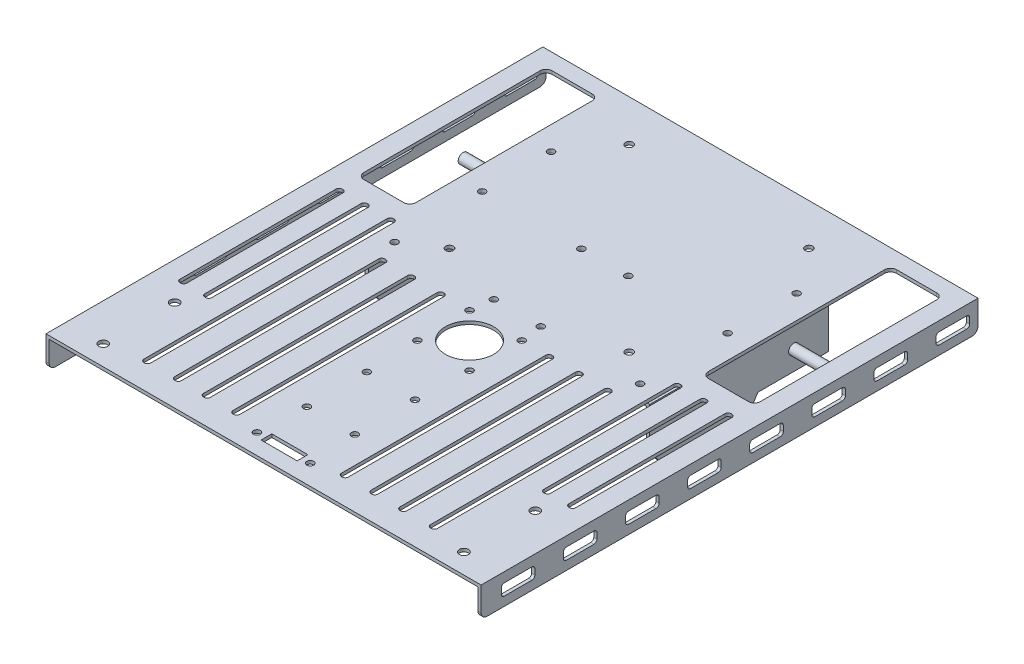
SolidWorks part; units mm, degrees
ref_plane "Front Plane" through (0, 0, 0) normal (0, 0, 1) x (1, 0, 0)
ref_plane "Top Plane" through (0, 0, 0) normal (0, 1, 0) x (1, 0, 0)
ref_plane "Right Plane" through (0, 0, 0) normal (1, 0, 0) x (0, 0, -1)
sketch "Sketch2" plane through (0, 0, 0) normal (0, 1, 0) x (1, 0, 0)
  line L7 (-172.2662, -88.2141) -> (41.7338, -88.2141)
  line L48 (-164.2662, 151.7859) -> (-138.2662, 151.7859)
  line L49 (-164.2662, 151.7859) -> (-164.2662, 57.7859)
  line L50 (-164.2662, 57.7859) -> (-138.2662, 57.7859)
  line L51 (-138.2662, 151.7859) -> (-138.2662, 57.7859)
  line L72 (41.7338, 159.7859) -> (-172.2662, 159.7859)
  line L75 (-65.2662, 159.7859) -> (-65.2662, -88.2141) construction
  line L76 (41.7338, -88.2141) -> (41.7338, 159.7859)
  line L77 (7.7338, 151.7859) -> (7.7338, 57.7859)
  line L78 (33.7338, 57.7859) -> (7.7338, 57.7859)
  line L79 (-172.2662, -88.2141) -> (-172.2662, 159.7859)
  line L80 (33.7338, 151.7859) -> (33.7338, 57.7859)
  line L81 (33.7338, 151.7859) -> (7.7338, 151.7859)
  point P2 (-151.2662, 151.7859)
  dimension "D1" = 8
  dimension "D3" = 8
  dimension "D6" = 107
  dimension "D9" = 26
extrude "Boss-Extrude1" add sketch "Sketch2" along normal blind 1.6
ref_plane "Plane3" through (-65.2662, 0, 0) normal (-1, 0, 0) x (0, 0, 1)
sketch "Sketch4" plane through (0, 0, 0) normal (0, -1, 0) x (1, 0, 0)
  line L5 (-172.2662, 15.9553) -> (41.7338, 15.9553) construction
  line L6 (-172.2662, -159.7859) -> (-172.2662, 88.2141) construction
  line L7 (41.7338, 88.2141) -> (41.7338, -159.7859) construction
  point P6 (-65.2662, 15.9553)
  line B0 (-136.2673, -122.8126) -> (-136.2673, -33.5103)
  line B1 (-136.2673, -122.8126) -> (-118.4267, -122.8126)
  line B2 (-136.2673, -33.5103) -> (-118.4299, -33.5103)
  line B3 (-72.7662, -32.9867) -> (-72.7662, -87.1773)
  line B4 (-72.7662, -32.9867) -> (-81.1807, -32.9867)
  line B5 (-72.7662, -87.1773) -> (-81.1807, -87.1773)
  line B6 (-118.4299, -33.5103) -> (-118.4299, -55.4044)
  line B7 (-118.4299, -55.4044) -> (-81.1807, -55.4044)
  line B8 (-81.1807, -55.4044) -> (-81.1807, -32.9867)
  line B9 (-81.1807, -87.1773) -> (-81.1807, -65.4044)
  line B10 (-81.1807, -65.4044) -> (-118.4267, -65.4044)
  line B11 (-118.4267, -65.4044) -> (-118.4267, -122.8126)
  dimension "D1" = 7.5
sketch_block_instance "Block1-1"
sketch_block "Block1"
extrude "Boss-Extrude3" add sketch "Sketch4" along normal blind 1.6129 separate body
sketch "Sketch6" plane through (-136.2673, 113.8349, 0) normal (1, 0, 0) x (0, -1, 0)
  line L0 (115.4478, 33.5103) -> (113.8349, 33.5103)
  line L1 (113.8349, 33.5103) -> (113.8349, 122.8126)
  line L4 (132.89, 33.5103) -> (115.4478, 33.5103)
  line L7 (135.5889, 122.8126) -> (113.8349, 122.8126)
  line L8 (113.8349, 57.7859) -> (113.8349, 151.7859) construction
  line L10 (115.4478, 122.8126) -> (113.8349, 122.8126) construction
  line L11 (135.5889, 122.8126) -> (135.5889, 87.5048)
  circle A2 centre (133.4041, 73.86) radius 1.27
  circle A4 centre (133.4041, 51.6858) radius 3
  circle A5 centre (125.8349, 105.4126) radius 2.55
  circle A6 centre (123.1933, 51.6858) radius 1.27
  circle A8 centre (143.6149, 51.6858) radius 1.27
  arc A10 (135.5889, 87.5048) -> (132.89, 33.5103) centre (121.2431, 61.1572) cw
  line M25 (113.8349, 33.5103) -> (113.8349, 122.8126)
  line M26 (113.8349, 122.8126) -> (115.4478, 122.8126)
  line M27 (115.4478, 122.8126) -> (115.4478, 33.5103)
  line M28 (115.4478, 33.5103) -> (113.8349, 33.5103)
  dimension "D1" = 5.1
  dimension "D3" = 17.4
  dimension "D4" = 6
  dimension "D2" = 12
extrude "Boss-Extrude4" add sketch "Sketch6" along normal blind 1.6129 contours M28 M25 M26 M27 | L4 M27 | A6 A2 A4 A8 region at (-136.2673, -15.7003, -74.0989) region at (-136.2673, -0.8065, -78.1615)
sketch "Sketch7" plane through (0, 0, 0) normal (0, -1, 0) x (1, 0, 0)
  line L0 (-172.2662, 88.2141) -> (41.7338, 88.2141) construction
  line L1 (-65.2662, -2.5939) -> (-65.2662, -26.5939)
  line L48 (-65.2662, -1159.7859) -> (-65.2662, 48840.2141) construction
  line L49 (41.7338, -159.7859) -> (-172.2662, -159.7859) construction
  line L50 (-65.2662, 80.4578) -> (-65.2662, 75.1009)
  line L51 (-65.2662, 80.4578) -> (-74.2715, 80.4578)
  line L52 (-65.2662, 75.1009) -> (-74.2715, 75.1009)
  line L53 (-74.2715, 80.4578) -> (-74.2715, 75.1009)
  circle A0 centre (-126.541, -82.125) radius 1.7
  circle A1 centre (-126.541, -38.4299) radius 1.7
  circle A2 centre (-76.9723, -38.4299) radius 1.7
  circle A3 centre (-76.9723, -82.125) radius 1.7
  circle A4 centre (-126.541, -116.5476) radius 1.7
  circle A5 centre (-110.1162, -49.4299) radius 1.9
  circle A6 centre (-110.1162, -139.1299) radius 1.9
  circle A7 centre (-155.2662, 42.5701) radius 2.25
  circle A8 centre (-78.2662, -1.5939) radius 1.7
  circle A9 centre (-78.2662, -27.5939) radius 1.7
  arc A11 (-65.2662, -2.5939) -> (-65.2662, -26.5939) centre (-65.2662, -14.5939) ccw
  circle A12 centre (-78.5662, 78.2141) radius 1.7
  circle A13 centre (-77.2662, 24.6349) radius 1.7
  circle A14 centre (-77.2662, 54.6349) radius 1.7
  circle A15 centre (-155.2662, 78.2141) radius 2.25
  point P38 (-65.2662, -159.7859)
  dimension "D3" = 3.4
  dimension "D4" = 3.4
  dimension "D5" = 3.4
  dimension "D6" = 3.4
  dimension "D1" = 3.4
  dimension "D2" = 3.8
  dimension "D8" = 3.8
  dimension "D9" = 4.5
  dimension "D12" = 3.4
  dimension "D13" = 3.4
  dimension "D14" = 12
  dimension "D20" = 3.4
  dimension "D23" = 3.4
  dimension "D24" = 3.4
  dimension "D22" = 10
  dimension "D25" = 30
  dimension "D15" = 13
  dimension "D19" = 12
  dimension "D21" = 13.3
  dimension "D11" = 89.7
  dimension "D17" = 13
  dimension "D18" = 26
  dimension "D7" = 92
  dimension "D16" = 44.85
  dimension "D26" = 11.7061
  dimension "D27" = 49.5687
  dimension "D10" = 90
  dimension "D28" = 34.836
extrude "Cut-Extrude1" cut sketch "Sketch7" against normal blind 10 and the other way blind 10
mirror "Mirror1" about plane through (-65.2662, 0, 0) normal (-1, 0, 0) of bodies 157 158 103
mirror "Mirror2" about plane through (-65.2662, 0, 0) normal (-1, 0, 0) of "Cut-Extrude1"
sketch "Sketch9" plane through (-138.2662, 0, 0) normal (1, 0, 0) x (0, 0, -1)
  circle A0 centre (105.4126, -12) radius 2.5
extrude "Boss-Extrude6" add sketch "Sketch9" along normal blind 169 and the other way blind 21 separate body
sketch "Sketch11" plane through (0, 1.6, 0) normal (0, 1, 0) x (1, 0, 0)
  line L0 (-172.2662, 159.7859) -> (-172.2662, -88.2141)
  line L1 (-172.2662, 159.7859) -> (-173.8662, 159.7859)
  line L2 (-172.2662, -88.2141) -> (-173.8662, -88.2141)
  line L3 (-173.8662, 159.7859) -> (-173.8662, -88.2141)
  line L4 (41.7338, 159.7859) -> (41.7338, -88.2141)
  line L5 (41.7338, 159.7859) -> (43.3338, 159.7859)
  line L6 (41.7338, -88.2141) -> (43.3338, -88.2141)
  line L7 (43.3338, 159.7859) -> (43.3338, -88.2141)
  dimension "D1" = 1.6
  dimension "D2" = 1.6
extrude "Boss-Extrude7" add sketch "Sketch11" against normal blind 15
sketch "Sketch12" plane through (0, 1.6, 0) normal (0, 1, 0) x (1, 0, 0)
  line L12 (-65.2662, -1088.2141) -> (-65.2662, 48911.7859) construction
  line L13 (-173.8662, -88.2141) -> (43.3338, -88.2141) construction
  line L30 (-164.0365, 46.7422) -> (-164.0365, -31.2149)
  line L31 (-162.5365, 48.2422) -> (-162.1365, 48.2422)
  line L32 (-162.5365, -32.7149) -> (-162.1365, -32.7149)
  line L33 (-160.6365, 46.7422) -> (-160.6365, -31.2149)
  line L34 (-151.5274, 46.7422) -> (-151.5274, -31.2149)
  line L35 (-150.0274, 48.2422) -> (-149.6274, 48.2422)
  line L36 (-150.0274, -32.7149) -> (-149.6274, -32.7149)
  line L37 (-148.1274, 46.7422) -> (-148.1274, -31.2149)
  line L38 (-138.5117, 46.7422) -> (-138.5117, -74.7128)
  line L39 (-137.0117, 48.2422) -> (-136.6117, 48.2422)
  line L40 (-137.0117, -76.2128) -> (-136.6117, -76.2128)
  line L41 (-135.1117, 46.7422) -> (-135.1117, -74.7128)
  line L42 (-123.2237, 27.2471) -> (-123.2237, -74.7128)
  line L43 (-121.7237, 28.7471) -> (-121.3237, 28.7471)
  line L44 (-121.7237, -76.2128) -> (-121.3237, -76.2128)
  line L45 (-119.8237, 27.2471) -> (-119.8237, -74.7128)
  line L46 (-108.7986, 27.2471) -> (-108.7986, -74.7128)
  line L47 (-107.2986, 28.7471) -> (-106.8986, 28.7471)
  line L48 (-107.2986, -76.2128) -> (-106.8986, -76.2128)
  line L49 (-105.3986, 27.2471) -> (-105.3986, -74.7128)
  line L50 (-94.0418, 27.2471) -> (-94.0418, -74.7128)
  line L51 (-92.5418, 28.7471) -> (-92.1418, 28.7471)
  line L52 (-92.5418, -76.2128) -> (-92.1418, -76.2128)
  line L53 (-90.6418, 27.2471) -> (-90.6418, -74.7128)
  line L54 (-39.8906, 27.2471) -> (-39.8906, -74.7128)
  line L55 (-37.9906, -76.2128) -> (-38.3906, -76.2128)
  line L56 (-37.9906, 28.7471) -> (-38.3906, 28.7471)
  line L57 (-36.4906, 27.2471) -> (-36.4906, -74.7128)
  line L58 (-25.1338, 27.2471) -> (-25.1338, -74.7128)
  line L59 (-23.2338, -76.2128) -> (-23.6338, -76.2128)
  line L60 (-23.2338, 28.7471) -> (-23.6338, 28.7471)
  line L61 (-21.7338, 27.2471) -> (-21.7338, -74.7128)
  line L62 (-10.7087, 27.2471) -> (-10.7087, -74.7128)
  line L63 (-8.8087, -76.2128) -> (-9.2087, -76.2128)
  line L64 (-8.8087, 28.7471) -> (-9.2087, 28.7471)
  line L65 (-7.3087, 27.2471) -> (-7.3087, -74.7128)
  line L66 (4.5793, 46.7422) -> (4.5793, -74.7128)
  line L67 (6.4793, -76.2128) -> (6.0793, -76.2128)
  line L68 (6.4793, 48.2422) -> (6.0793, 48.2422)
  line L69 (7.9793, 46.7422) -> (7.9793, -74.7128)
  line L70 (17.5951, 46.7422) -> (17.5951, -31.2149)
  line L71 (19.4951, -32.7149) -> (19.0951, -32.7149)
  line L72 (19.4951, 48.2422) -> (19.0951, 48.2422)
  line L73 (20.9951, 46.7422) -> (20.9951, -31.2149)
  line L74 (30.1041, 46.7422) -> (30.1041, -31.2149)
  line L75 (32.0041, -32.7149) -> (31.6041, -32.7149)
  line L76 (32.0041, 48.2422) -> (31.6041, 48.2422)
  line L77 (33.5041, 46.7422) -> (33.5041, -31.2149)
  arc A0 (-94.0418, -74.7128) -> (-92.5418, -76.2128) centre (-92.5418, -74.7128) ccw
  arc A1 (-92.1418, -76.2128) -> (-90.6418, -74.7128) centre (-92.1418, -74.7128) ccw
  arc A2 (-92.1418, 28.7471) -> (-90.6418, 27.2471) centre (-92.1418, 27.2471) cw
  arc A3 (-94.0418, 27.2471) -> (-92.5418, 28.7471) centre (-92.5418, 27.2471) cw
  arc A4 (-108.7986, 27.2471) -> (-107.2986, 28.7471) centre (-107.2986, 27.2471) cw
  arc A5 (-106.8986, 28.7471) -> (-105.3986, 27.2471) centre (-106.8986, 27.2471) cw
  arc A6 (-106.8986, -76.2128) -> (-105.3986, -74.7128) centre (-106.8986, -74.7128) ccw
  arc A7 (-108.7986, -74.7128) -> (-107.2986, -76.2128) centre (-107.2986, -74.7128) ccw
  arc A8 (-123.2237, -74.7128) -> (-121.7237, -76.2128) centre (-121.7237, -74.7128) ccw
  arc A9 (-121.3237, -76.2128) -> (-119.8237, -74.7128) centre (-121.3237, -74.7128) ccw
  arc A10 (-121.3237, 28.7471) -> (-119.8237, 27.2471) centre (-121.3237, 27.2471) cw
  arc A11 (-123.2237, 27.2471) -> (-121.7237, 28.7471) centre (-121.7237, 27.2471) cw
  arc A12 (-138.5117, -74.7128) -> (-137.0117, -76.2128) centre (-137.0117, -74.7128) ccw
  arc A13 (-136.6117, -76.2128) -> (-135.1117, -74.7128) centre (-136.6117, -74.7128) ccw
  arc A14 (-136.6117, 48.2422) -> (-135.1117, 46.7422) centre (-136.6117, 46.7422) cw
  arc A15 (-138.5117, 46.7422) -> (-137.0117, 48.2422) centre (-137.0117, 46.7422) cw
  arc A16 (-151.5274, 46.7422) -> (-150.0274, 48.2422) centre (-150.0274, 46.7422) cw
  arc A17 (-149.6274, 48.2422) -> (-148.1274, 46.7422) centre (-149.6274, 46.7422) cw
  arc A18 (-149.6274, -32.7149) -> (-148.1274, -31.2149) centre (-149.6274, -31.2149) ccw
  arc A19 (-151.5274, -31.2149) -> (-150.0274, -32.7149) centre (-150.0274, -31.2149) ccw
  arc A20 (-164.0365, -31.2149) -> (-162.5365, -32.7149) centre (-162.5365, -31.2149) ccw
  arc A21 (-162.1365, -32.7149) -> (-160.6365, -31.2149) centre (-162.1365, -31.2149) ccw
  arc A22 (-162.1365, 48.2422) -> (-160.6365, 46.7422) centre (-162.1365, 46.7422) cw
  arc A23 (-162.5365, 48.2422) -> (-164.0365, 46.7422) centre (-162.5365, 46.7422) ccw
  arc A24 (32.0041, 48.2422) -> (33.5041, 46.7422) centre (32.0041, 46.7422) cw
  arc A25 (31.6041, 48.2422) -> (30.1041, 46.7422) centre (31.6041, 46.7422) ccw
  arc A26 (31.6041, -32.7149) -> (30.1041, -31.2149) centre (31.6041, -31.2149) cw
  arc A27 (33.5041, -31.2149) -> (32.0041, -32.7149) centre (32.0041, -31.2149) cw
  arc A28 (20.9951, -31.2149) -> (19.4951, -32.7149) centre (19.4951, -31.2149) cw
  arc A29 (19.0951, -32.7149) -> (17.5951, -31.2149) centre (19.0951, -31.2149) cw
  arc A30 (19.0951, 48.2422) -> (17.5951, 46.7422) centre (19.0951, 46.7422) ccw
  arc A31 (20.9951, 46.7422) -> (19.4951, 48.2422) centre (19.4951, 46.7422) ccw
  arc A32 (7.9793, 46.7422) -> (6.4793, 48.2422) centre (6.4793, 46.7422) ccw
  arc A33 (6.0793, 48.2422) -> (4.5793, 46.7422) centre (6.0793, 46.7422) ccw
  arc A34 (6.0793, -76.2128) -> (4.5793, -74.7128) centre (6.0793, -74.7128) cw
  arc A35 (7.9793, -74.7128) -> (6.4793, -76.2128) centre (6.4793, -74.7128) cw
  arc A36 (-7.3087, 27.2471) -> (-8.8087, 28.7471) centre (-8.8087, 27.2471) ccw
  arc A37 (-9.2087, 28.7471) -> (-10.7087, 27.2471) centre (-9.2087, 27.2471) ccw
  arc A38 (-9.2087, -76.2128) -> (-10.7087, -74.7128) centre (-9.2087, -74.7128) cw
  arc A39 (-7.3087, -74.7128) -> (-8.8087, -76.2128) centre (-8.8087, -74.7128) cw
  arc A40 (-21.7338, -74.7128) -> (-23.2338, -76.2128) centre (-23.2338, -74.7128) cw
  arc A41 (-23.6338, -76.2128) -> (-25.1338, -74.7128) centre (-23.6338, -74.7128) cw
  arc A42 (-23.6338, 28.7471) -> (-25.1338, 27.2471) centre (-23.6338, 27.2471) ccw
  arc A43 (-21.7338, 27.2471) -> (-23.2338, 28.7471) centre (-23.2338, 27.2471) ccw
  arc A44 (-36.4906, 27.2471) -> (-37.9906, 28.7471) centre (-37.9906, 27.2471) ccw
  arc A45 (-38.3906, 28.7471) -> (-39.8906, 27.2471) centre (-38.3906, 27.2471) ccw
  arc A46 (-38.3906, -76.2128) -> (-39.8906, -74.7128) centre (-38.3906, -74.7128) cw
  arc A47 (-36.4906, -74.7128) -> (-37.9906, -76.2128) centre (-37.9906, -74.7128) cw
  point P41 (-65.2662, -88.2141)
  dimension "D1" = 1.5
extrude "Cut-Extrude2" cut sketch "Sketch12" against normal blind 8
sketch "Sketch13" plane through (-173.8662, 0, 0) normal (-1, 0, 0) x (0, 0, 1)
  line L0 (-154.0943, -3.2309) -> (-140.3411, -3.2309)
  line L1 (-155.5943, -4.7309) -> (-155.5943, -7.4516)
  line L2 (-138.8411, -4.7309) -> (-138.8411, -7.4516)
  line L3 (-154.0943, -8.9516) -> (-140.3411, -8.9516)
  line L4 (-107.8411, -4.7309) -> (-107.8411, -7.4516)
  line L5 (-123.0943, -8.9516) -> (-109.3411, -8.9516)
  line L6 (-124.5943, -4.7309) -> (-124.5943, -7.4516)
  line L7 (-123.0943, -3.2309) -> (-109.3411, -3.2309)
  line L8 (-76.8411, -4.7309) -> (-76.8411, -7.4516)
  line L9 (-92.0943, -8.9516) -> (-78.3411, -8.9516)
  line L10 (-93.5943, -4.7309) -> (-93.5943, -7.4516)
  line L11 (-92.0943, -3.2309) -> (-78.3411, -3.2309)
  line L12 (-45.8411, -4.7309) -> (-45.8411, -7.4516)
  line L13 (-61.0943, -8.9516) -> (-47.3411, -8.9516)
  line L14 (-62.5943, -4.7309) -> (-62.5943, -7.4516)
  line L15 (-61.0943, -3.2309) -> (-47.3411, -3.2309)
  line L16 (-14.8411, -4.7309) -> (-14.8411, -7.4516)
  line L17 (-30.0943, -8.9516) -> (-16.3411, -8.9516)
  line L18 (-31.5943, -4.7309) -> (-31.5943, -7.4516)
  line L19 (-30.0943, -3.2309) -> (-16.3411, -3.2309)
  line L20 (16.1589, -4.7309) -> (16.1589, -7.4516)
  line L21 (0.9057, -8.9516) -> (14.6589, -8.9516)
  line L22 (-0.5943, -4.7309) -> (-0.5943, -7.4516)
  line L23 (0.9057, -3.2309) -> (14.6589, -3.2309)
  line L24 (47.1589, -4.7309) -> (47.1589, -7.4516)
  line L25 (31.9057, -8.9516) -> (45.6589, -8.9516)
  line L26 (30.4057, -4.7309) -> (30.4057, -7.4516)
  line L27 (31.9057, -3.2309) -> (45.6589, -3.2309)
  line L28 (78.1589, -4.7309) -> (78.1589, -7.4516)
  line L29 (62.9057, -8.9516) -> (76.6589, -8.9516)
  line L30 (61.4057, -4.7309) -> (61.4057, -7.4516)
  line L31 (62.9057, -3.2309) -> (76.6589, -3.2309)
  arc A0 (-155.5943, -7.4516) -> (-154.0943, -8.9516) centre (-154.0943, -7.4516) ccw
  arc A1 (-138.8411, -7.4516) -> (-140.3411, -8.9516) centre (-140.3411, -7.4516) cw
  arc A2 (-140.3411, -3.2309) -> (-138.8411, -4.7309) centre (-140.3411, -4.7309) cw
  arc A3 (-155.5943, -4.7309) -> (-154.0943, -3.2309) centre (-154.0943, -4.7309) cw
  arc A4 (-107.8411, -7.4516) -> (-109.3411, -8.9516) centre (-109.3411, -7.4516) cw
  arc A5 (-124.5943, -7.4516) -> (-123.0943, -8.9516) centre (-123.0943, -7.4516) ccw
  arc A6 (-124.5943, -4.7309) -> (-123.0943, -3.2309) centre (-123.0943, -4.7309) cw
  arc A7 (-109.3411, -3.2309) -> (-107.8411, -4.7309) centre (-109.3411, -4.7309) cw
  arc A8 (-76.8411, -7.4516) -> (-78.3411, -8.9516) centre (-78.3411, -7.4516) cw
  arc A9 (-93.5943, -7.4516) -> (-92.0943, -8.9516) centre (-92.0943, -7.4516) ccw
  arc A10 (-93.5943, -4.7309) -> (-92.0943, -3.2309) centre (-92.0943, -4.7309) cw
  arc A11 (-78.3411, -3.2309) -> (-76.8411, -4.7309) centre (-78.3411, -4.7309) cw
  arc A12 (-45.8411, -7.4516) -> (-47.3411, -8.9516) centre (-47.3411, -7.4516) cw
  arc A13 (-62.5943, -7.4516) -> (-61.0943, -8.9516) centre (-61.0943, -7.4516) ccw
  arc A14 (-62.5943, -4.7309) -> (-61.0943, -3.2309) centre (-61.0943, -4.7309) cw
  arc A15 (-47.3411, -3.2309) -> (-45.8411, -4.7309) centre (-47.3411, -4.7309) cw
  arc A16 (-14.8411, -7.4516) -> (-16.3411, -8.9516) centre (-16.3411, -7.4516) cw
  arc A17 (-31.5943, -7.4516) -> (-30.0943, -8.9516) centre (-30.0943, -7.4516) ccw
  arc A18 (-31.5943, -4.7309) -> (-30.0943, -3.2309) centre (-30.0943, -4.7309) cw
  arc A19 (-16.3411, -3.2309) -> (-14.8411, -4.7309) centre (-16.3411, -4.7309) cw
  arc A20 (16.1589, -7.4516) -> (14.6589, -8.9516) centre (14.6589, -7.4516) cw
  arc A21 (-0.5943, -7.4516) -> (0.9057, -8.9516) centre (0.9057, -7.4516) ccw
  arc A22 (-0.5943, -4.7309) -> (0.9057, -3.2309) centre (0.9057, -4.7309) cw
  arc A23 (14.6589, -3.2309) -> (16.1589, -4.7309) centre (14.6589, -4.7309) cw
  arc A24 (47.1589, -7.4516) -> (45.6589, -8.9516) centre (45.6589, -7.4516) cw
  arc A25 (30.4057, -7.4516) -> (31.9057, -8.9516) centre (31.9057, -7.4516) ccw
  arc A26 (30.4057, -4.7309) -> (31.9057, -3.2309) centre (31.9057, -4.7309) cw
  arc A27 (45.6589, -3.2309) -> (47.1589, -4.7309) centre (45.6589, -4.7309) cw
  arc A28 (78.1589, -7.4516) -> (76.6589, -8.9516) centre (76.6589, -7.4516) cw
  arc A29 (61.4057, -7.4516) -> (62.9057, -8.9516) centre (62.9057, -7.4516) ccw
  arc A30 (61.4057, -4.7309) -> (62.9057, -3.2309) centre (62.9057, -4.7309) cw
  arc A31 (76.6589, -3.2309) -> (78.1589, -4.7309) centre (76.6589, -4.7309) cw
  dimension "D1" = 1.5
  dimension "D2" = 8
extrude "Cut-Extrude3" cut sketch "Sketch13" against normal blind 222
fillet "Fillet1" radius 3 12 edges at (-173.0662, -13.4, 88.2141) (-173.0662, -13.4, -159.7859) (42.5338, -13.4, -159.7859) (42.5338, -13.4, 88.2141) (-138.2662, 0.8, -57.7859) (-164.2662, 0.8, -151.7859) (-164.2662, 0.8, -57.7859) (-138.2662, 0.8, -151.7859) (33.7338, 0.8, -151.7859) (7.7338, 0.8, -151.7859) (33.7338, 0.8, -57.7859) (7.7338, 0.8, -57.7859)
equation "\"hardboard_width\"= 3.175"
equation "\"D1@Boss-Extrude1\"=\"hardboard_width\""
equation "\"steel_24g_thickness\"= 0.5"
equation "\"m3_clearance_hole\"= 3.4"
equation "\"D3@Sketch7\"=\"m3_clearance_hole\""
equation "\"D4@Sketch7\"=\"m3_clearance_hole\""
equation "\"D5@Sketch7\"=\"m3_clearance_hole\""
equation "\"D6@Sketch7\"=\"m3_clearance_hole\""
equation "\"steel_16g_thickness\"=1.6129"
equation "\"D1@Boss-Extrude3\"=\"steel_16g_thickness\""
equation "\"D1@Boss-Extrude4\"=\"steel_16g_thickness\""
equation "\"D1@Sketch7\"=\"m3_clearance_hole\""
equation "\"D12@Sketch7\"=\"m3_clearance_hole\""
equation "\"D20@Sketch7\"=\"m3_clearance_hole\""
equation "\"D23@Sketch7\"=\"m3_clearance_hole\""
equation "\"D24@Sketch7\"=\"m3_clearance_hole\""
equation "\"D13@Sketch7\"=\"m3_clearance_hole\""
equation "\"D28@Sketch7\"=80-44.85-0.314"
